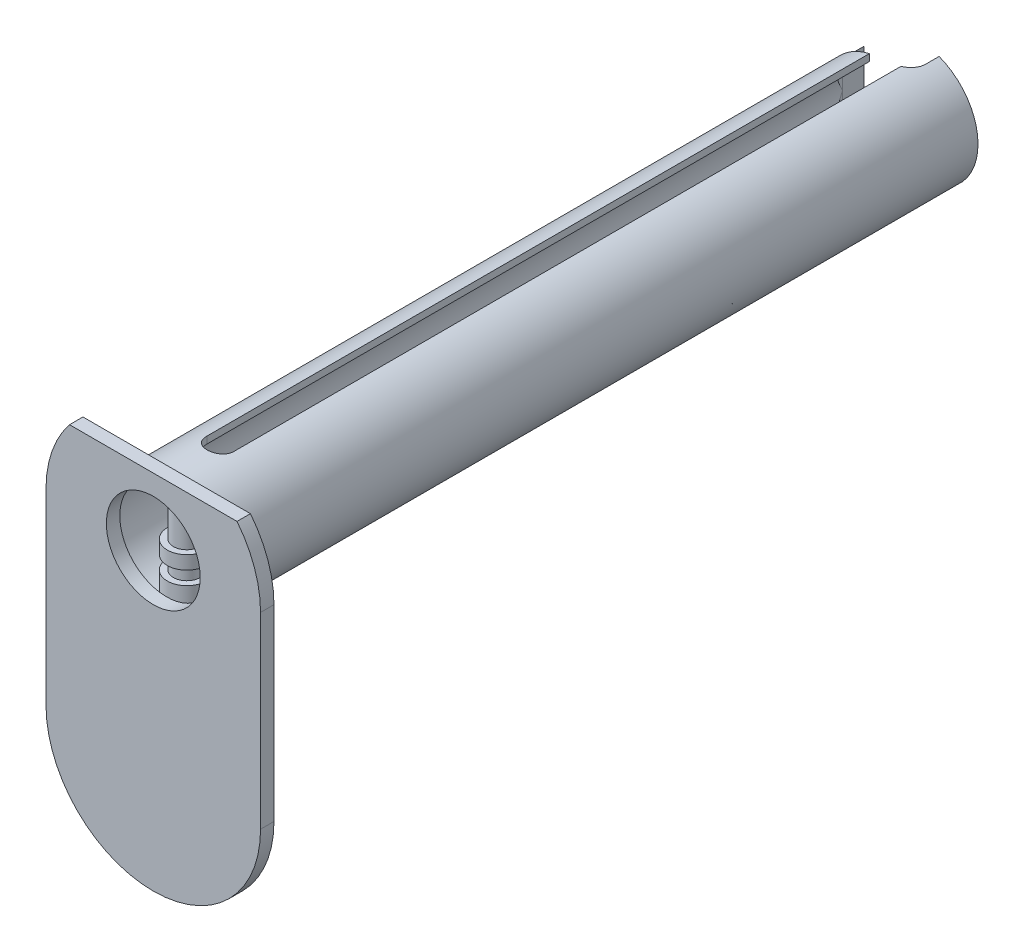
SolidWorks part; units mm, degrees
material "Laiton"
ref_plane "Plan de face" through (0, 0, 0) normal (0, 0, 1) x (1, 0, 0)
ref_plane "Plan de dessus" through (0, 0, 0) normal (0, 1, 0) x (1, 0, 0)
ref_plane "Plan de droite" through (0, 0, 0) normal (1, 0, 0) x (0, 0, -1)
sketch "Esquisse1" plane through (0, 0, 0) normal (0, 0, 1) x (1, 0, 0)
  circle A0 centre (0, 0) radius 4
  circle A1 centre (0, 0) radius 4.5
  dimension "D2" = 9
  dimension "D3" = 0.5
extrude "Boss.-Extru.1" add sketch "Esquisse1" along normal mid plane 56
sketch "Esquisse2" plane through (0, 0, 0) normal (0, 1, 0) x (1, 0, 0)
  line L0 (-4, -28) -> (4, -28) construction
  line L1 (0, 0) -> (8.5203, 0) construction
  line L2 (4, 28) -> (-4, 28) construction
  circle A0 centre (0, -26.5) radius 1
  circle A1 centre (3, 26.5) radius 0.5
  dimension "D1" = 2
  dimension "D4" = 1
  dimension "D2" = 1.5
  dimension "D3" = 1.5
  dimension "D5" = 3
extrude "Boss.-Extru.2" add sketch "Esquisse2" along normal up to next and the other way up to next
sketch "Esquisse3" plane through (0, 0, 0) normal (0, 1, 0) x (1, 0, 0)
  line L0 (0, 28) -> (0, -24) construction
  line L1 (1, 28) -> (1, -24)
  line L2 (-1, 28) -> (-1, -24)
  line L3 (4.5, 28) -> (-4.5, 28) construction
  arc A0 (1, 28) -> (-1, 28) centre (0, 28) ccw
  arc A1 (-1, -24) -> (1, -24) centre (0, -24) ccw
  circle A2 centre (0, -26.5) radius 1 construction
  point P3 (0, 2)
  dimension "D2" = 2.5
  dimension "D1" = 2
extrude "Enlèv. mat.-Extru.1" cut sketch "Esquisse3" against normal through all and the other way through all
sketch "Esquisse4" plane through (0, 0, 28) normal (0, 0, 1) x (1, 0, 0)
  line L0 (0, 0) -> (0, -14) construction
  line L1 (8, 0) -> (8, -14)
  line L2 (-8, 0) -> (-8, -14)
  arc A0 (8, 0) -> (-8, 0) centre (0, 0) ccw
  arc A1 (-8, -14) -> (8, -14) centre (0, -14) ccw
  circle A2 centre (0, 0) radius 3.5
  point P2 (0, -7)
  dimension "D1" = 8
  dimension "D3" = 7
  dimension "D2" = 14
extrude "Boss.-Extru.3" add sketch "Esquisse4" along normal blind 1
sketch "Esquisse6" plane through (0, 0, 29) normal (0, 0, 1) x (1, 0, 0)
  line L0 (-8, 0) -> (-8, -14) construction
  line L1 (-8, 5) -> (8, 5)
  line L2 (-8, 5) -> (-8, -22)
  line L3 (-8, -22) -> (8, -22)
  line L4 (8, 5) -> (8, -22)
  line L5 (8, -14) -> (8, 0) construction
  arc A0 (-8, -14) -> (8, -14) centre (0, -14) ccw construction
  dimension "D1" = 5
extrude "Enlèv. mat.-Extru.2" cut sketch "Esquisse6" against normal through all flip side to cut
sketch "Esquisse7" plane through (0, 0, 0) normal (0, 1, 0) x (1, 0, 0)
  circle A0 centre (0, -26.5) radius 1.45
  circle A1 centre (0, -26.5) radius 1 construction
  dimension "D1" = 2.9
extrude "Boss.-Extru.6" add sketch "Esquisse7" along normal blind 1 from offset 1.5 offset against normal yes
sketch "Esquisse8" plane through (0, -1.5, 0) normal (0, -1, 0) x (1, 0, 0)
  circle A0 centre (0, 26.5) radius 1.45 construction
  circle A1 centre (0, 26.5) radius 1.45
extrude "Boss.-Extru.7" add sketch "Esquisse8" along normal up to next from offset 1
sketch "Esquisse9" plane through (0, 0, 0) normal (0, 1, 0) x (1, 0, 0)
  line L1 (0, 25.4) -> (-3, 25.4)
  line L2 (1.6, 27) -> (1.6, 28)
  line L3 (-4, 28) -> (-4, 26.4)
  line L4 (4, 28) -> (1, 28) construction
  line L5 (1.6, 28) -> (-4, 28)
  arc A0 (0, 25.4) -> (1.6, 27) centre (0, 27) ccw
  arc A1 (-4, 26.4) -> (-3, 25.4) centre (-3, 26.4) ccw
  circle A2 centre (0, 27) radius 1 construction
  dimension "D2" = 1.6
  dimension "D4" = 1
  dimension "D3" = 4
extrude "Enlèv. mat.-Extru.3" cut sketch "Esquisse9" against normal through all and the other way through all
